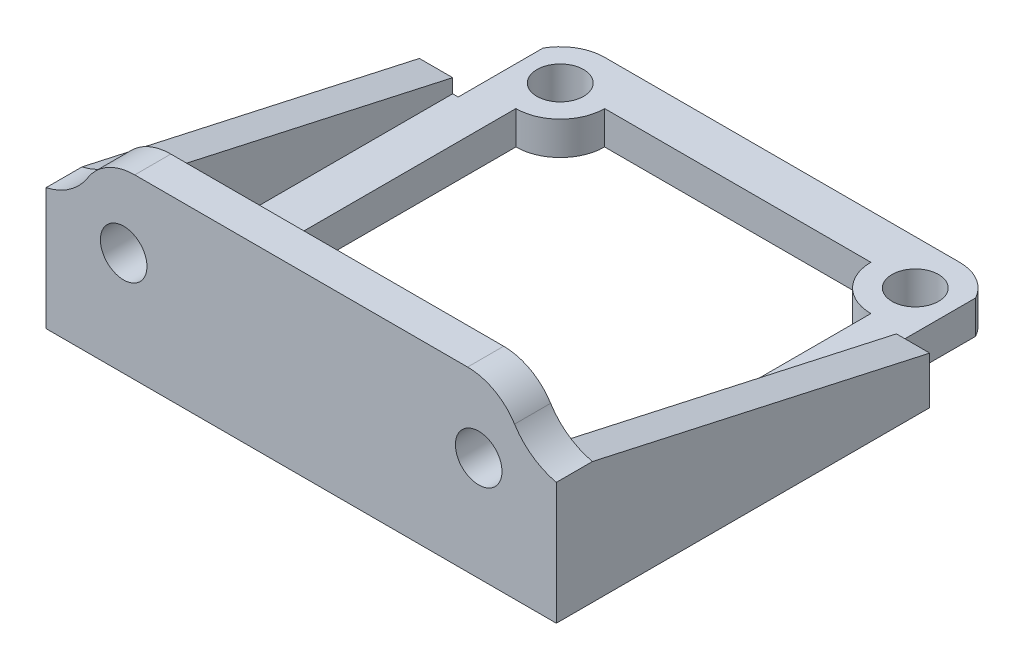
SolidWorks part; units mm, degrees
ref_plane "Front" through (0, 0, 0) normal (0, 0, 1) x (1, 0, 0)
ref_plane "Top" through (0, 0, 0) normal (0, 1, 0) x (1, 0, 0)
ref_plane "Right" through (0, 0, 0) normal (1, 0, 0) x (0, 0, -1)
sketch "Sketch1" plane through (0, 0, 0) normal (0, 1, 0) x (1, 0, 0)
  line L0 (0, 20) -> (32, 20)
  line L2 (36, 16) -> (36, -16)
  line L4 (-4, 16) -> (-4, -16)
  line L6 (0, 12) -> (0, -12)
  line L7 (4, 16) -> (28, 16)
  line L8 (32, 12) -> (32, -12)
  line L9 (4, -16) -> (28, -16)
  line L10 (-4, -16) -> (-4, -23.3516)
  line L11 (-4, -23.3516) -> (36, -23.3516)
  line L12 (36, -23.3516) -> (36, -16)
  circle A0 centre (0, 16) radius 2.1
  circle A1 centre (0, -16) radius 2.1
  circle A3 centre (32, 16) radius 2.1
  circle A4 centre (32, -16) radius 2.1
  arc A5 (0, 20) -> (-4, 16) centre (0, 16) ccw
  arc A6 (4, -16) -> (0, -12) centre (0, -16) ccw
  arc A8 (28, 16) -> (32, 12) centre (32, 16) ccw
  arc A9 (0, 12) -> (4, 16) centre (0, 16) ccw
  arc A10 (36, 16) -> (32, 20) centre (32, 16) ccw
  arc A11 (32, -12) -> (28, -16) centre (32, -16) ccw
  point P4 (0, 0)
extrude "Boss-Extrude1" add sketch "Sketch1" along normal blind 3
sketch "Sketch2" plane through (0, 3, 0) normal (0, 1, 0) x (1, 0, 0)
  line L0 (36, -23.3516) -> (36, 16) construction
  line L1 (-4, -23.3516) -> (36, -23.3516)
  line L2 (-4, -23.3516) -> (-4, -20.1016)
  line L3 (-4, -20.1016) -> (36, -20.1016)
  line L4 (36, -23.3516) -> (36, -20.1016)
extrude "Boss-Extrude2" add sketch "Sketch2" along normal blind 13
sketch "Sketch3" plane through (0, 0, 20.1016) normal (0, 0, -1) x (-1, 0, 0)
  circle A0 centre (-0.0006, 9.3962) radius 2.1
  circle A1 centre (-31.9994, 9.3962) radius 2.1
extrude "Cut-Extrude1" cut sketch "Sketch3" against normal blind 15
fillet "Fillet1" radius 5 2 edges at (36, 16, 21.7266) (-4, 16, 21.7266)
sketch "Sketch4" plane through (36, 0, 0) normal (1, 0, 0) x (0, 0, -1)
  line L0 (-20.1016, 11) -> (12, 3.8864)
  line L2 (12, 0) -> (-23.3516, 0)
  line L3 (-23.3516, 11) -> (-23.3516, 0) construction
  line L4 (-23.3516, 0) -> (16, 0) construction
  line L5 (-23.3516, 0) -> (-23.3516, 11)
  line L6 (-23.3516, 11) -> (-20.1016, 11)
  line L8 (12, 0) -> (12, 3.8864)
extrude "Boss-Extrude3" add sketch "Sketch4" along normal blind 3
sketch "Sketch5" plane through (-4, 0, 0) normal (-1, 0, 0) x (0, 0, 1)
  line L3 (20.1016, 11) -> (23.3516, 11)
  line L4 (23.3516, 11) -> (23.3516, 0)
  line L5 (23.3516, 0) -> (-12, 0)
  line L6 (-12, 3.8864) -> (20.1016, 11)
  line L8 (-12, 0) -> (-12, 3.8864)
extrude "Boss-Extrude4" add sketch "Sketch5" along normal blind 3
fillet "Fillet4" radius 6 2 edges at (36, 11, 21.7266) (-4, 11, 21.7266)
sketch "Sketch7" plane through (0, 3, 0) normal (0, 1, 0) x (1, 0, 0)
  line L14 (-7, 10.3021) -> (-3.5, 10.3021)
  line L15 (-7, -20.1016) -> (-7, 12) construction
  line L16 (-3.5, 10.3021) -> (-3.5, 20.1657)
  line L17 (-3.5, 20.1657) -> (-7, 20.1657)
  line L18 (-7, 20.1657) -> (-7, 10.3021)
  line L19 (16, 16) -> (16, -49984) construction
  line L20 (28, 16) -> (4, 16) construction
  line L21 (39, 20.1657) -> (39, 10.3021)
  line L22 (35.5, 20.1657) -> (39, 20.1657)
  line L23 (35.5, 10.3021) -> (35.5, 20.1657)
  line L24 (39, 10.3021) -> (35.5, 10.3021)
  point P21 (16, 16)
extrude "Cut-Extrude2" cut sketch "Sketch7" against normal blind 10
sketch "Sketch8" plane through (0, 3, 0) normal (0, -1, 0) x (-1, 0, 0)
  line L1 (4, 12) -> (7, 12)
  line L2 (4, 12) -> (4, 10.3021)
  line L3 (4, 10.3021) -> (7, 10.3021)
  line L4 (7, 12) -> (7, 10.3021)
  line L5 (-36, 12) -> (-39, 12)
  line L6 (-36, 12) -> (-36, 10.3021)
  line L7 (-36, 10.3021) -> (-39, 10.3021)
  line L8 (-39, 12) -> (-39, 10.3021)
extrude "Cut-Extrude3" cut sketch "Sketch8" against normal blind 10
